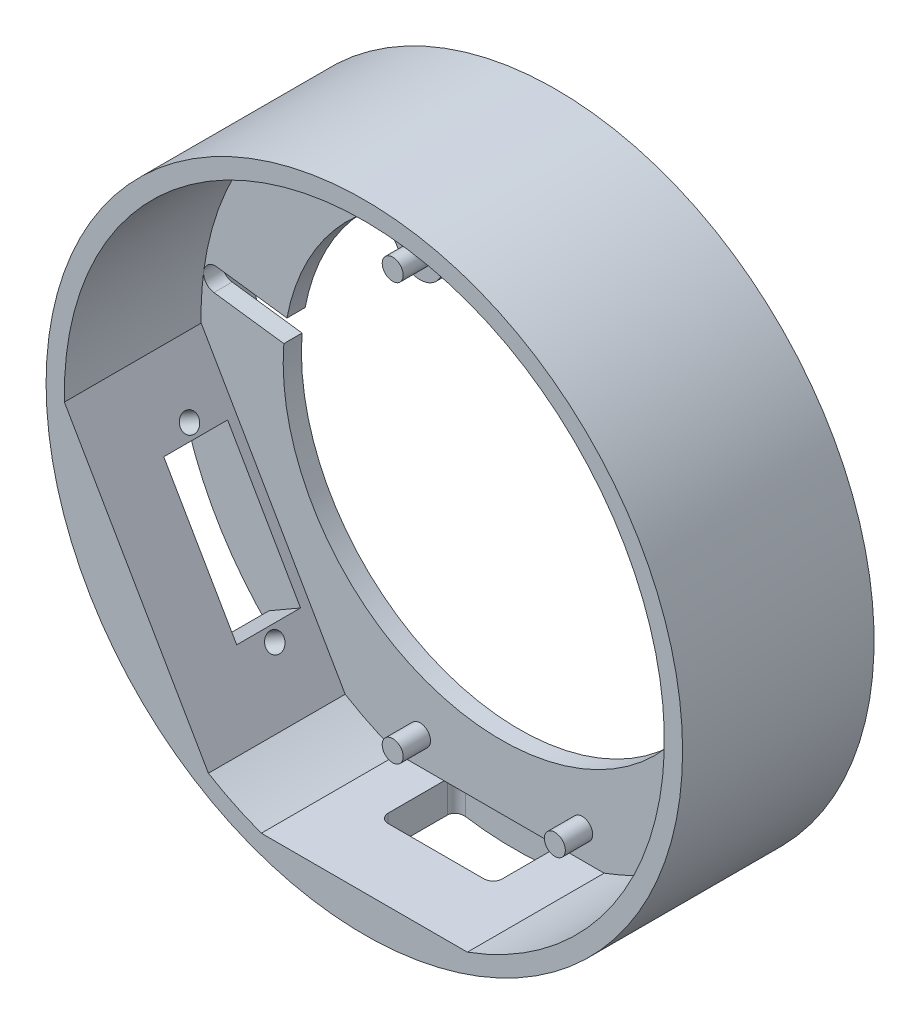
SolidWorks part; units mm, degrees
ref_plane "Plan de face" through (0, 0, 0) normal (0, 0, 1) x (1, 0, 0)
ref_plane "Plan de dessus" through (0, 0, 0) normal (0, 1, 0) x (1, 0, 0)
ref_plane "Plan de droite" through (0, 0, 0) normal (1, 0, 0) x (0, 0, -1)
sketch "Esquisse_carte_affichage" plane through (0, 0, 0) normal (0, 0, 1) x (1, 0, 0)
  circle A0 centre (19.25, 25.1) radius 0.5
  circle A1 centre (25.07, -19.23) radius 0.5
  circle A2 centre (29.18, 12.09) radius 0.5
  circle A3 centre (31.32, -4.14) radius 0.5
  circle A4 centre (-29.21, -12.07) radius 0.5
  circle A5 centre (-31.32, 4.14) radius 0.5
  circle A6 centre (-26.4935, -7.4094) radius 0.25
  circle A7 centre (-23.6728, -14.0139) radius 0.25
  circle A8 centre (-19.2392, -19.6637) radius 0.25
  circle A9 centre (-13.4943, -23.973) radius 0.25
  circle A10 centre (-6.8298, -26.6487) radius 0.25
  circle A11 centre (0.3, -27.5085) radius 0.25
  circle A12 centre (7.4094, -26.4935) radius 0.25
  circle A13 centre (14.0139, -23.6728) radius 0.25
  circle A14 centre (19.6637, -19.2392) radius 0.25
  circle A15 centre (23.973, -13.4943) radius 0.25
  circle A16 centre (26.6487, -6.8298) radius 0.25
  circle A17 centre (27.5085, 0.3) radius 0.25
  circle A18 centre (26.4935, 7.4094) radius 0.25
  circle A19 centre (23.6728, 14.0139) radius 0.25
  circle A20 centre (19.2392, 19.6637) radius 0.25
  circle A21 centre (13.4943, 23.973) radius 0.25
  circle A22 centre (6.8298, 26.6487) radius 0.25
  circle A23 centre (-0.3, 27.5085) radius 0.25
  circle A24 centre (-7.4094, 26.4935) radius 0.25
  circle A25 centre (-14.0139, 23.6728) radius 0.25
  circle A26 centre (-19.6637, 19.2392) radius 0.25
  circle A27 centre (-23.973, 13.4943) radius 0.25
  circle A28 centre (-26.6487, 6.8298) radius 0.25
  circle A29 centre (-27.5085, -0.3) radius 0.25
  circle A30 centre (-30.2, -7.1) radius 0.25
  circle A31 centre (-26.5986, -15.746) radius 0.25
  circle A32 centre (-28.1305, -7.8674) radius 0.25
  circle A33 centre (-21.6169, -22.0937) radius 0.25
  circle A34 centre (-25.1358, -14.8801) radius 0.25
  circle A35 centre (-15.162, -26.9359) radius 0.25
  circle A36 centre (-20.428, -20.8785) radius 0.25
  circle A37 centre (-7.6738, -29.9423) radius 0.25
  circle A38 centre (-14.3281, -25.4544) radius 0.25
  circle A39 centre (0.3371, -30.9082) radius 0.25
  circle A40 centre (-7.252, -28.2956) radius 0.25
  circle A41 centre (8.3254, -29.7678) radius 0.25
  circle A42 centre (0.3185, -29.2082) radius 0.25
  circle A43 centre (15.746, -26.5986) radius 0.25
  circle A44 centre (7.8674, -28.1305) radius 0.25
  circle A45 centre (22.0937, -21.6169) radius 0.25
  circle A46 centre (14.8801, -25.1358) radius 0.25
  circle A47 centre (26.9359, -15.162) radius 0.25
  circle A48 centre (20.8785, -20.428) radius 0.25
  circle A49 centre (29.9423, -7.6738) radius 0.25
  circle A50 centre (25.4544, -14.3281) radius 0.25
  circle A51 centre (30.9082, 0.3371) radius 0.25
  circle A52 centre (28.2956, -7.252) radius 0.25
  circle A53 centre (29.7678, 8.3254) radius 0.25
  circle A54 centre (29.2082, 0.3185) radius 0.25
  circle A55 centre (26.5986, 15.746) radius 0.25
  circle A56 centre (28.1305, 7.8674) radius 0.25
  circle A57 centre (21.6169, 22.0937) radius 0.25
  circle A58 centre (25.1358, 14.8801) radius 0.25
  circle A59 centre (15.162, 26.9359) radius 0.25
  circle A60 centre (20.428, 20.8785) radius 0.25
  circle A61 centre (7.6738, 29.9423) radius 0.25
  circle A62 centre (14.3281, 25.4544) radius 0.25
  circle A63 centre (-0.3371, 30.9082) radius 0.25
  circle A64 centre (7.252, 28.2956) radius 0.25
  circle A65 centre (-8.3254, 29.7678) radius 0.25
  circle A66 centre (-0.3185, 29.2082) radius 0.25
  circle A67 centre (-15.746, 26.5986) radius 0.25
  circle A68 centre (-7.8674, 28.1305) radius 0.25
  circle A69 centre (-22.0937, 21.6169) radius 0.25
  circle A70 centre (-14.8801, 25.1358) radius 0.25
  circle A71 centre (-26.9359, 15.162) radius 0.25
  circle A72 centre (-20.8785, 20.428) radius 0.25
  circle A73 centre (-29.9423, 7.6738) radius 0.25
  circle A74 centre (-25.4544, 14.3281) radius 0.25
  circle A75 centre (-30.9082, -0.3371) radius 0.25
  circle A76 centre (-28.2956, 7.252) radius 0.25
  circle A77 centre (0, 0) radius 26.162
  circle A78 centre (0, 0) radius 32.766
  dimension "D1" = 65.532
  dimension "D2" = 52.324
sketch "Esquisse_carte_mère" plane through (0, 0, 0) normal (0, 0, 1) x (1, 0, 0)
  line L0 (-11.3435, -28.5174) -> (-11.0897, -29.13)
  line L1 (-11.0897, -29.13) -> (-10.6861, -29.6561)
  line L2 (-10.6861, -29.6561) -> (-10.16, -30.0597)
  line L3 (-10.16, -30.0597) -> (-9.5474, -30.3135)
  line L4 (-9.5474, -30.3135) -> (-8.89, -30.4)
  line L5 (-8.89, -30.4) -> (-2.413, -30.4)
  line L6 (-2.413, -30.4) -> (-1.905, -29.892)
  line L7 (-1.905, -29.892) -> (1.905, -29.892)
  line L8 (1.905, -29.892) -> (2.413, -30.4)
  line L9 (2.413, -30.4) -> (8.89, -30.4)
  line L10 (8.89, -30.4) -> (9.5474, -30.3135)
  line L11 (9.5474, -30.3135) -> (10.16, -30.0597)
  line L12 (10.16, -30.0597) -> (10.6861, -29.6561)
  line L13 (10.6861, -29.6561) -> (11.0897, -29.13)
  line L14 (11.0897, -29.13) -> (11.3435, -28.5174)
  line L15 (11.3435, -28.5174) -> (11.43, -27.86)
  line L16 (11.43, -27.86) -> (11.43, 17.86)
  line L17 (11.43, 17.86) -> (11.3435, 18.5174)
  line L18 (11.3435, 18.5174) -> (11.0897, 19.13)
  line L19 (11.0897, 19.13) -> (10.6861, 19.6561)
  line L20 (10.6861, 19.6561) -> (10.16, 20.0597)
  line L21 (10.16, 20.0597) -> (9.5474, 20.3135)
  line L22 (9.5474, 20.3135) -> (8.89, 20.4)
  line L23 (8.89, 20.4) -> (-8.89, 20.4)
  line L24 (-8.89, 20.4) -> (-9.5474, 20.3135)
  line L25 (-9.5474, 20.3135) -> (-10.16, 20.0597)
  line L26 (-10.16, 20.0597) -> (-10.6861, 19.6561)
  line L27 (-10.6861, 19.6561) -> (-11.0897, 19.13)
  line L28 (-11.0897, 19.13) -> (-11.3435, 18.5174)
  line L29 (-11.3435, 18.5174) -> (-11.43, 17.86)
  line L30 (-11.43, 17.86) -> (-11.43, -27.86)
  line L31 (-11.43, -27.86) -> (-11.3435, -28.5174)
  line L32 (8.9522, -28.0199) -> (-18113.3609, 46572.2136) construction
  line L33 (-8.9266, -27.9541) -> (18113.3865, 46572.2795) construction
  circle A0 centre (-3.3, -25.05) radius 0.4
  circle A1 centre (3.3, -25.05) radius 0.4
  circle A2 centre (-3.6, -27.86) radius 0.45
  circle A3 centre (3.6, -27.86) radius 0.45
  circle A4 centre (10.16, 14.05) radius 0.5
  circle A5 centre (10.16, 11.51) radius 0.5
  circle A6 centre (10.16, 8.97) radius 0.5
  circle A7 centre (10.16, 6.43) radius 0.5
  circle A8 centre (10.16, 3.89) radius 0.5
  circle A9 centre (10.16, 1.35) radius 0.5
  circle A10 centre (10.16, -1.19) radius 0.5
  circle A11 centre (10.16, -3.73) radius 0.5
  circle A12 centre (10.16, -6.27) radius 0.5
  circle A13 centre (10.16, -8.81) radius 0.5
  circle A14 centre (10.16, -11.35) radius 0.5
  circle A15 centre (10.16, -13.89) radius 0.5
  circle A16 centre (-10.16, -24.05) radius 0.5
  circle A17 centre (-10.16, -21.51) radius 0.5
  circle A18 centre (-10.16, -18.97) radius 0.5
  circle A19 centre (-10.16, -16.43) radius 0.5
  circle A20 centre (-10.16, -13.89) radius 0.5
  circle A21 centre (-10.16, -11.35) radius 0.5
  circle A22 centre (-10.16, -8.81) radius 0.5
  circle A23 centre (-10.16, -6.27) radius 0.5
  circle A24 centre (-10.16, -3.73) radius 0.5
  circle A25 centre (-10.16, -1.19) radius 0.5
  circle A26 centre (-10.16, 1.35) radius 0.5
  circle A27 centre (-10.16, 3.89) radius 0.5
  circle A28 centre (-10.16, 6.43) radius 0.5
  circle A29 centre (-10.16, 8.97) radius 0.5
  circle A30 centre (-10.16, 11.51) radius 0.5
  circle A31 centre (-10.16, 14.05) radius 0.5
  circle A32 centre (-8.89, -27.86) radius 1.25
  circle A33 centre (8.89, -27.86) radius 1.25
  circle A34 centre (-8.89, 17.86) radius 1.25
  circle A35 centre (8.89, 17.86) radius 1.25
  circle A36 centre (-1.95, -25.955) radius 0.35
  circle A37 centre (1.95, -25.955) radius 0.35
  circle A38 centre (-2.2, 15.706) radius 0.45
  circle A39 centre (3.048, -15.795) radius 0.25
  circle A40 centre (1.016, -20.875) radius 0.25
  circle A41 centre (-6.223, -9.826) radius 0.25
  circle A42 centre (-6.096, -16.43) radius 0.25
  circle A43 centre (7.3914, -2.0028) radius 0.25
  circle A44 centre (7.366, -18.462) radius 0.25
  circle A45 centre (-1.905, 12.018) radius 0.25
  circle A46 centre (1.905, 9.224) radius 0.25
  circle A47 centre (-5.715, -21.129) radius 0.25
  circle A48 centre (-4.064, -1.571) radius 0.25
  circle A49 centre (-8.509, -22.78) radius 0.25
  circle A50 centre (0.2286, -14.5758) radius 0.25
  circle A51 centre (0.508, 7.446) radius 0.25
  circle A52 centre (0.635, 8.589) radius 0.25
  circle A53 centre (-7.112, 0.334) radius 0.25
  circle A54 centre (4.953, -15.795) radius 0.25
  circle A55 centre (0, 10.494) radius 0.25
  circle A56 centre (-4.191, -16.43) radius 0.25
  circle A57 centre (-0.889, -17.573) radius 0.25
  circle A58 centre (5.842, -10.715) radius 0.25
  circle A59 centre (2.159, -17.446) radius 0.25
  circle A60 centre (0, -27.987) radius 0.25
  circle A61 centre (-1.397, 4.271) radius 0.25
  circle A62 centre (-5.207, 1.985) radius 0.25
  circle A63 centre (-0.381, -6.651) radius 0.25
  circle A64 centre (6.858, 8.462) radius 0.25
  circle A65 centre (5.207, 3.128) radius 0.25
  circle A66 centre (2.667, 4.525) radius 0.25
  circle A67 centre (5.08, 11.764) radius 0.25
  circle A68 centre (0, 14.431) radius 0.25
  circle A69 centre (-1.778, 8.716) radius 0.25
  circle A70 centre (-2.921, 4.271) radius 0.25
  circle A71 centre (-5.588, 3.128) radius 0.25
  circle A72 centre (-1.905, -19.732) radius 0.25
  circle A73 centre (-5.842, -8.683) radius 0.25
  circle A74 centre (-3.048, -20.113) radius 0.25
  circle A75 centre (-6.604, -7.667) radius 0.25
  circle A76 centre (-5.207, -10.842) radius 0.25
  circle A77 centre (10.668, -26.082) radius 0.25
  circle A78 centre (5.969, -4.365) radius 0.25
  circle A79 centre (5.08, -9.191) radius 0.25
  circle A80 centre (-3.81, -3.349) radius 0.25
  circle A81 centre (-4.953, -9.699) radius 0.25
  circle A82 centre (3.048, 6.43) radius 0.25
  circle A83 centre (5.969, -3.222) radius 0.25
  circle A84 centre (6.858, -7.667) radius 0.25
  circle A85 centre (6.477, 6.303) radius 0.25
  circle A86 centre (-1.27, 10.367) radius 0.25
  circle A87 centre (-1.0922, -0.1994) radius 0.25
  circle A88 centre (0.508, -0.428) radius 0.25
  circle A89 centre (4.318, -17.065) radius 0.25
  circle A90 centre (1.524, 4.144) radius 0.25
  circle A91 centre (-2.921, -1.444) radius 0.25
  circle A92 centre (3.302, -10.08) radius 0.25
  circle A93 centre (-3.81, -10.08) radius 0.25
  circle A94 centre (-5.08, -6.778) radius 0.25
  point P222 (0, -5)
  dimension "D5" = 2.5
  dimension "D1" = 2.54
  dimension "D2" = 2.54
  dimension "D3" = 2.54
  dimension "D4" = 2.54
sketch "Esquisse_support" plane through (0, 0, 0) normal (0, 0, 1) x (1, 0, 0)
  line L0 (0, 0) -> (0, -50000) construction
  line L1 (0, 0) -> (-31.32, 4.14) construction
  line L2 (0, 0) -> (19.25, 25.1) construction
  line L3 (0, 0) -> (25.07, -19.23) construction
  line L4 (25.07, -19.23) -> (30456.2807, 39653.7005) construction
  line L5 (19.25, 25.1) -> (39694.4792, -30403.1136) construction
  line L6 (-31.32, 4.14) -> (6520.8813, 49572.9675) construction
  line L7 (-31.1487, 5.4363) -> (-23.4871, 4.4235)
  line L8 (-31.4913, 2.8437) -> (-23.8298, 1.831)
  line L9 (18.2437, 25.8718) -> (13.5179, 19.7098)
  line L10 (20.2563, 24.3282) -> (15.5305, 18.1663)
  line L11 (25.8637, -18.1952) -> (19.7291, -13.4897)
  line L12 (24.2763, -20.2648) -> (18.1417, -15.5592)
  line L13 (-8.89, 17.86) -> (46591.3436, 18140.1731) construction
  line L14 (8.89, 17.86) -> (-46591.3436, 18140.1731) construction
  line L15 (11.22, 16.9539) -> (13.5179, 19.7098)
  line L16 (72498.2044, -186428.9542) -> (-90602.6131, 232973.148) construction
  line L17 (-72498.1788, -186428.8884) -> (90602.6387, 232973.2138) construction
  circle A0 centre (0, 0) radius 32.9 construction
  circle A1 centre (0, 0) radius 34.9
  arc A2 (-32.6163, 4.3113) -> (-31.4913, 2.8437) centre (-31.32, 4.14) ccw
  arc A3 (-32.6163, 4.3113) -> (-31.1487, 5.4363) centre (-31.32, 4.14) cw
  arc A4 (20.0218, 26.1063) -> (18.2437, 25.8718) centre (19.25, 25.1) ccw
  arc A5 (20.0218, 26.1063) -> (20.2563, 24.3282) centre (19.25, 25.1) cw
  arc A6 (26.1048, -20.0237) -> (25.8637, -18.1952) centre (25.07, -19.23) ccw
  arc A7 (26.1048, -20.0237) -> (24.2763, -20.2648) centre (25.07, -19.23) cw
  arc A8 (-23.4871, 4.4235) -> (13.5179, 19.7098) centre (0, 0) cw construction
  arc A9 (-23.8298, 1.831) -> (18.1417, -15.5592) centre (0, 0) ccw
  arc A10 (19.7291, -13.4897) -> (15.5305, 18.1663) centre (0, 0) ccw
  arc A11 (-6.56, 18.7661) -> (-11.22, 16.9539) centre (-8.89, 17.86) cw
  arc A12 (6.56, 18.7661) -> (11.22, 16.9539) centre (8.89, 17.86) ccw
  arc A13 (-6.56, 18.7661) -> (-4.1838, 23.531) centre (-3.28, 20.1053) cw
  arc A14 (6.56, 18.7661) -> (4.1838, 23.531) centre (3.28, 20.1053) ccw
  arc A15 (-11.22, 16.9539) -> (-15.8818, 17.86) centre (-13.8724, 15.7529) ccw
  arc A16 (-23.4871, 4.4235) -> (-15.8818, 17.86) centre (0, 0) cw
  arc A17 (-4.1838, 23.531) -> (4.1838, 23.531) centre (0, 0) cw
  point P37 (-4.1838, 23.531)
  dimension "D1" = 65.8
  dimension "D2" = 69.8
  dimension "D12" = 2.5
  dimension "D13" = 2.5
  dimension "D3" = 90
  dimension "D4" = 90
  dimension "D5" = 90
  dimension "D7" = 90
  dimension "D8" = 90
  dimension "D9" = 90
  dimension "D10" = 90
  dimension "D11" = 90
extrude "Boss.-Extru.1" add sketch "Esquisse_support" along normal blind 2 contours A1 A13 A17 A14 A12 L15 L9 A4 A5 L10 A10 L11 A6 A7 L12 A9 L8 A2 A3 L7 A16 A15 A11 region at (-33.9129, 0, 0)
sketch "Esquisse6" plane through (0, 0, 2) normal (0, 0, 1) x (1, 0, 0)
  line L0 (0, 0) -> (0, -50000) construction
  circle A0 centre (-8.89, 17.86) radius 1.15
  circle A1 centre (-8.89, -27.86) radius 1.15
  circle A2 centre (8.89, -27.86) radius 1.15
  circle A3 centre (8.89, 17.86) radius 1.15
  dimension "D1" = 2.3
  dimension "D2" = 2.3
extrude "Boss.-Extru.2" add sketch "Esquisse6" along normal blind 3
sketch "Esquisse7" plane through (0, 0, 0) normal (0, 0, -1) x (-1, 0, 0)
  circle A0 centre (0, 0) radius 34.9
  circle A1 centre (0, 0) radius 32.9
extrude "Boss.-Extru.3" add sketch "Esquisse7" along normal blind 4
sketch "Esquisse8" plane through (0, 0, 2) normal (0, 0, 1) x (1, 0, 0)
  line L0 (0, 0) -> (0, -50000) construction
  line L1 (-11.296, -30.9) -> (11.296, -30.9)
  line L2 (-8.89, -30.4) -> (-2.413, -30.4) construction
  circle A0 centre (0, 0) radius 34.9
  circle A1 centre (0, 0) radius 32.9 construction
  arc A2 (-11.296, -30.9) -> (11.296, -30.9) centre (0, 0) cw
  point P9 (0, -30.9)
  point P16 (-25.8603, -16.6011)
  point P21 (-22.4942, -14.4402)
  circle M5 centre (0, 0) radius 34.9
  dimension "D2" = 0.5
extrude "Boss.-Extru.5" add sketch "Esquisse8" along normal blind 15 contours L1 M5 region at (-33.9129, 0, 2)
sketch "Ouverture_USB" plane through (0, -30.9, 0) normal (0, 1, 0) x (1, 0, 0)
  line L0 (0, -16.2747) -> (0, 5.3613) construction
  line L2 (-5.25, -9.13) -> (5.25, -9.13)
  line L3 (-6.25, -8.13) -> (-6.25, -1.63)
  line L4 (-5.25, -0.63) -> (5.25, -0.63)
  line L5 (6.25, -8.13) -> (6.25, -1.63)
  arc A0 (6.25, -8.13) -> (5.25, -9.13) centre (5.25, -8.13) cw
  arc A1 (6.25, -1.63) -> (5.25, -0.63) centre (5.25, -1.63) ccw
  arc A2 (-5.25, -0.63) -> (-6.25, -1.63) centre (-5.25, -1.63) ccw
  arc A3 (-6.25, -8.13) -> (-5.25, -9.13) centre (-5.25, -8.13) ccw
  dimension "D4" = 1
  dimension "D1" = 8.5
  dimension "D2" = 12.5
  dimension "D3" = 0.63
extrude "Enlèv. mat.-Extru.1" cut sketch "Ouverture_USB" against normal blind 10
sketch "Esquisse9" plane through (0, 0, 2) normal (0, 0, 1) x (1, 0, 0)
  line L0 (0, -1000) -> (0, 49000) construction
  line L1 (0, 0) -> (-43301.2702, -25000) construction
  line L2 (-34.3348, -6.2555) -> (-22.5848, -26.6071) construction
  line L3 (-32.8913, -0.7557) -> (-17.1001, -28.1069)
  arc A0 (-32.6163, 4.3113) -> (-11.296, -30.9) centre (0, 0) ccw construction
  arc A1 (-32.8913, -0.7557) -> (-17.1001, -28.1069) centre (0, 0) ccw
  circle A2 centre (0, 0) radius 34.9 construction
  point P1 (0, 0)
  point P5 (0, 0)
  point P11 (-28.4598, -16.4313)
  point P12 (0, 0)
  point P14 (-24.9957, -14.4313)
  point P19 (0, 0)
  arc M10 (-32.6163, 4.3113) -> (-11.296, -30.9) centre (0, 0) ccw
  dimension "D1" = 60
  dimension "D2" = 23.5
  dimension "D4" = 4
extrude "Boss.-Extru.6" add sketch "Esquisse9" along direction (0, 0, 1) on the side of the normal through all contours L3 M10 region at (-26.4019, -15.2432, 2)
sketch "Esquisse10" plane through (-24.9957, -14.4313, 0) normal (0.866, 0.5, 0) x (0, 0, -1)
  line L1 (-6.5, -15.7912) -> (-6.5, 15.7912) construction
  line L2 (-3, -8) -> (-10, -8)
  line L3 (-3, -8) -> (-3, 8)
  line L4 (-3, 8) -> (-10, 8)
  line L5 (-10, -8) -> (-10, 8)
  line L6 (-3, -8) -> (-10, 8) construction
  line L7 (-3, 8) -> (-10, -8) construction
  line L9 (-3, 0) -> (-10, 0) construction
  line L11 (-17, -15.7912) -> (-2, -15.7912) construction
  circle A0 centre (-6.5, -9.35) radius 1
  circle A1 centre (-6.5, 9.35) radius 1
  point P0 (0, 0)
  point P4 (-6.5, 0)
  point P14 (-6.5, 0)
  point P19 (-6.5, 0)
  point P21 (-6.5, 0)
  point P26 (0, 0)
  point P27 (0, 0)
  point P28 (-7.1669, -6.3157)
  point P29 (0, 0)
  point P30 (0, 0)
  dimension "D3" = 9.35
  dimension "D4" = 2
  dimension "D1" = 16
  dimension "D2" = 7
extrude "Enlèv. mat.-Extru.2" cut sketch "Esquisse10" against normal through all
sketch "Esquisse12" plane through (-4, 6.9282, 0) normal (0.5, -0.866, 0) x (0.866, 0.5, 0)
  line L0 (-28.8626, 3) -> (-28.8626, 10) construction
  line L1 (-32.8626, 10) -> (-37.8626, 10)
  line L2 (-32.8626, 10) -> (-32.8626, 3)
  line L3 (-32.8626, 3) -> (-37.8626, 3)
  line L4 (-37.8626, 10) -> (-37.8626, 3)
  line L5 (-33.9707, 10) -> (-28.8626, 10) construction
  line L6 (-33.9707, 3) -> (-28.8626, 3) construction
  point P6 (0, 0)
  point P9 (0, 0)
  dimension "D1" = 4
  dimension "D2" = 5
extrude "Enlèv. mat.-Extru.3" cut sketch "Esquisse12" against normal through all both and the other way through all
